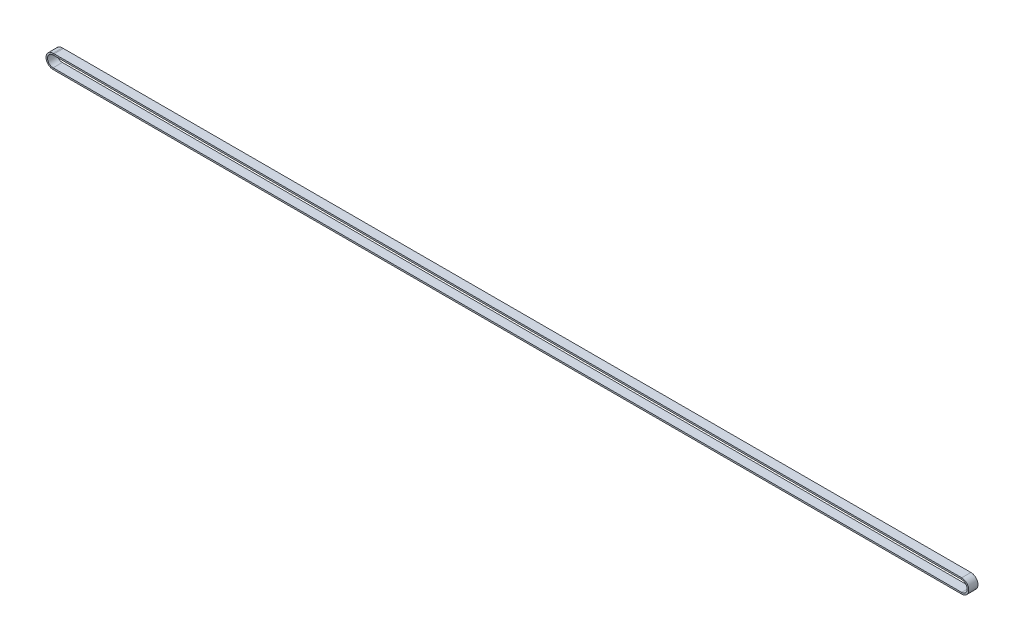
SolidWorks part; units mm, degrees
ref_plane "Front Plane" through (0, 0, 0) normal (0, 0, 1) x (1, 0, 0)
ref_plane "Top Plane" through (0, 0, 0) normal (0, 1, 0) x (1, 0, 0)
ref_plane "Right Plane" through (0, 0, 0) normal (1, 0, 0) x (0, 0, -1)
sketch "Sketch2" plane through (0, 0, -146.2334) normal (0, 0, 1) x (1, 0, 0)
  line L0 (0, 0) -> (1, 0) construction
  line L1 (0, 0) -> (0, 1) construction
  line L2 (-1, 148.3793) -> (883.5206, 148.3793)
  line L3 (883.5206, 134.5793) -> (-1, 134.5793)
  arc A0 (-1, 134.5793) -> (-1, 148.3793) centre (-1, 141.4793) cw
  arc A1 (883.5206, 148.3793) -> (883.5206, 134.5793) centre (883.5206, 141.4793) cw
sketch "Sketch3" plane through (0, 0, 0) normal (1, 0, 0) x (0, 0, -1)
  line L1 (146.2334, 146.8793) -> (137.2334, 146.8793)
  line L2 (146.2334, 146.8793) -> (146.2334, 148.3793)
  line L3 (146.2334, 148.3793) -> (137.2334, 148.3793)
  line L4 (137.2334, 146.8793) -> (137.2334, 148.3793)
  dimension "D1" = 9
  dimension "D2" = 1.5
sweep "Sweep1" add profiles "Sketch3" path "Sketch2"
